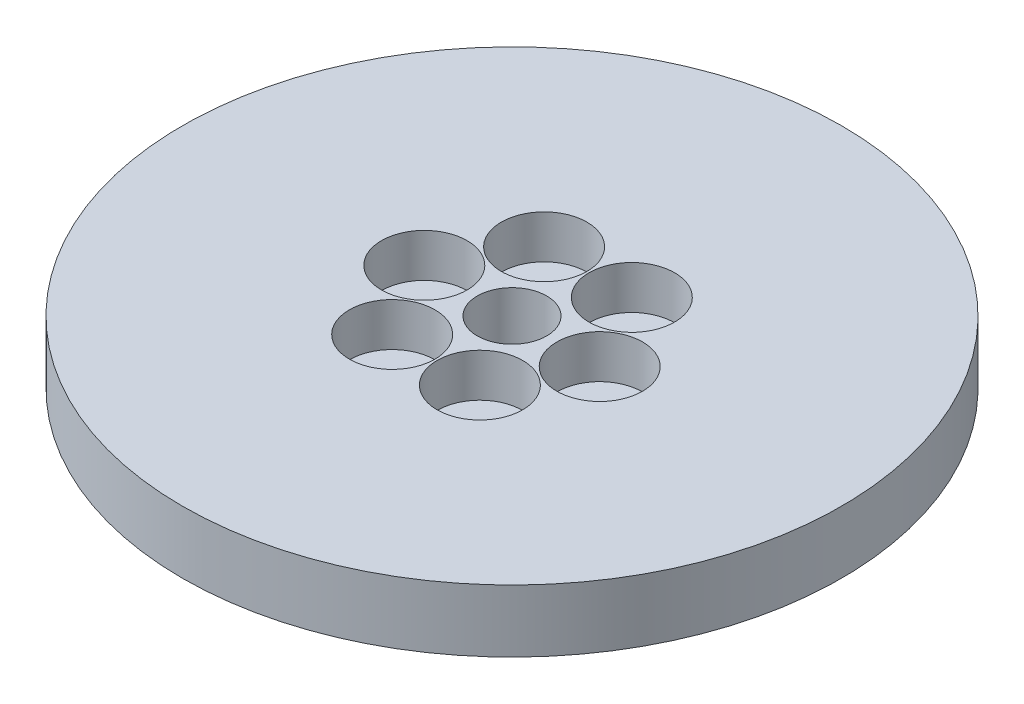
SolidWorks part; units mm, degrees
ref_plane "Front Plane" through (0, 0, 0) normal (0, 0, 1) x (1, 0, 0)
ref_plane "Top Plane" through (0, 0, 0) normal (0, 1, 0) x (1, 0, 0)
ref_plane "Right Plane" through (0, 0, 0) normal (1, 0, 0) x (0, 0, -1)
sketch "Sketch1" plane through (0, 0, 0) normal (0, 1, 0) x (1, 0, 0)
  circle A0 centre (0, 0) radius 47.5
  dimension "FLANGE_OD" = 95
extrude "Boss-Extrude1" add sketch "Sketch1" along normal blind 9
sketch "Sketch2" plane through (0, 0, 0) normal (0, 1, 0) x (1, 0, 0)
  circle A0 centre (0, 0) radius 5
  dimension "BORE_D" = 10
extrude "Cut-Extrude1" cut sketch "Sketch2" along normal through all
sketch "Sketch3" plane through (0, 9, 0) normal (0, 1, 0) x (1, 0, 0)
  circle A0 centre (0, 0) radius 12.6419 construction
  circle A1 centre (-12.6419, 0) radius 6.1683
  dimension "BOLT_D" = 12.3367
  dimension "BOLT_PCD" = 25.2838
extrude "Cut-Extrude2" cut sketch "Sketch3" against normal blind 6.2415
pattern_circular "CirPattern1" count 6 over 360 about axis through (0, 0, 0) along (0, 1, 0) of "Cut-Extrude2"
